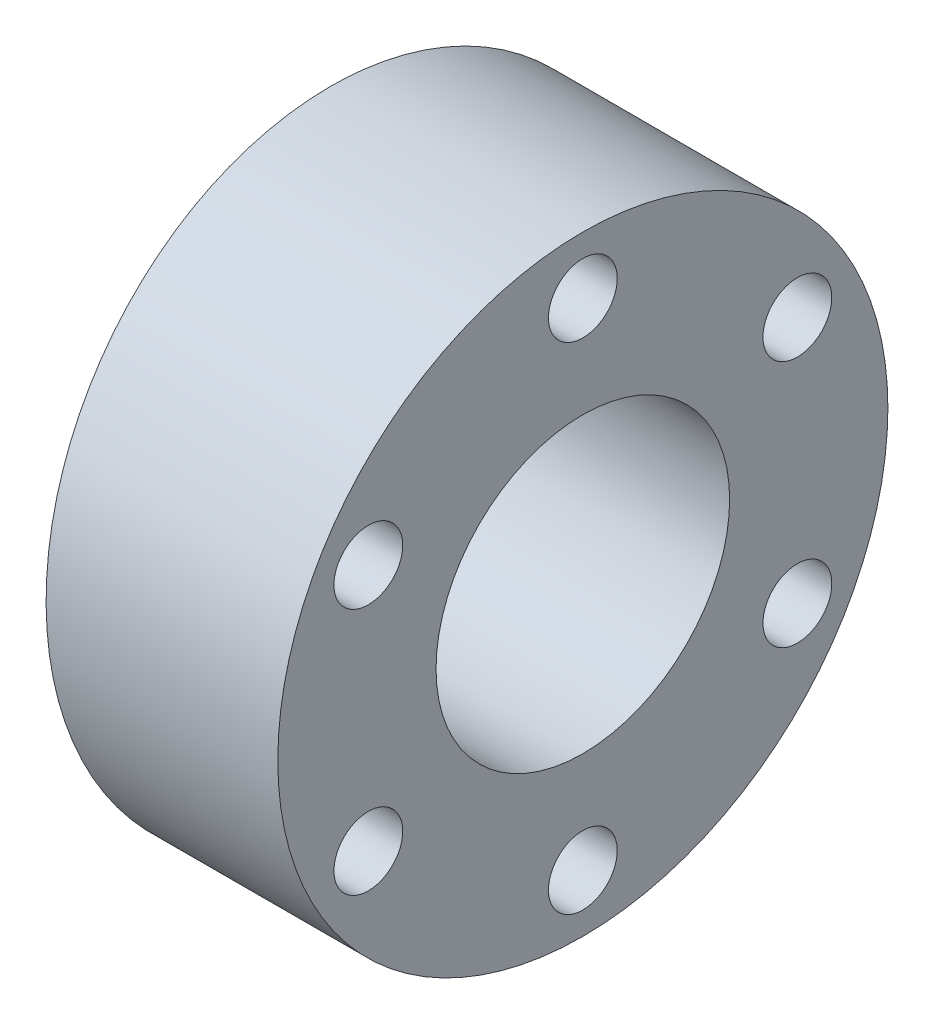
SolidWorks part; units mm, degrees
ref_plane "Front Plane" through (0, 0, 0) normal (0, 0, 1) x (1, 0, 0)
ref_plane "Top Plane" through (0, 0, 0) normal (0, 1, 0) x (1, 0, 0)
ref_plane "Right Plane" through (0, 0, 0) normal (1, 0, 0) x (0, 0, -1)
sketch "Sketch1" plane through (0, 0, 0) normal (1, 0, 0) x (0, 0, -1)
  circle A0 centre (0, 0) radius 16.891
extrude "Boss-Extrude1" add sketch "Sketch1" along normal blind 13.97 contours A0
sketch "Sketch2" plane through (13.97, 0, 0) normal (1, 0, 0) x (0, 0, -1)
  circle A0 centre (0, 0) radius 8.128
extrude "Cut-Extrude1" cut sketch "Sketch2" against normal through all
sketch "Sketch3" plane through (0, 0, 0) normal (0, 0, 1) x (1, 0, 0)
  line L0 (0, 16.891) -> (2.3623, -16.891)
  line L1 (0, -16.891) -> (13.97, -16.891) construction
  line L2 (2.3623, -16.891) -> (0, -16.891)
  line L3 (0, -16.891) -> (0, 16.891)
  line L4 (0, 16.891) -> (0, -42.5714) construction
  dimension "D1" = 4
extrude "Cut-Extrude2" cut sketch "Sketch3" against normal through all both and the other way through all
ref_point "Point2"
sketch "Sketch4" plane through (0, 0, 0) normal (0, 0, 1) x (1, 0, 0)
  line L0 (0, 34.756) -> (0, -35.3196) construction
  line L1 (0, -38.1381) -> (0, 38.1381) construction
ref_plane "Plane2" through (16.51, 0, 0) normal (1, 0, 0) x (0, 0, -1)
ref_plane "Plane3" through (0, 0, 0) normal (0, 0, 1) x (1, 0, 0)
sketch "Sketch5" plane through (0, 0, 0) normal (0, 0, 1) x (1, 0, 0)
  line L0 (13.97, -16.891) -> (-3.7141, -16.891)
sketch "Sketch6" plane through (0, 0, 0) normal (0, 0, 1) x (1, 0, 0)
  line L0 (2.3623, -16.891) -> (0, 16.891)
  line L1 (0, 34.756) -> (0, -35.3196) construction
  line L2 (0, 16.891) -> (2.3623, -16.891) construction
sketch "Sketch7" plane through (13.97, 0, 0) normal (1, 0, 0) x (0, 0, -1)
  line L0 (0, 34.756) -> (0, -35.3196) construction
  circle A0 centre (0, 13.716) radius 1.905
  dimension "D1" = 13.716
extrude "Cut-Extrude3" cut sketch "Sketch7" against normal through all contours A0
ref_axis "Axis1" through (0.6128, 0, 0) along (1, 0, 0)
pattern_circular "CirPattern1" count 6 every 60 about axis through (0.6128, 0, 0) along (1, 0, 0) of "Cut-Extrude3"
ref_point "Point4"
ref_point "Point6"
